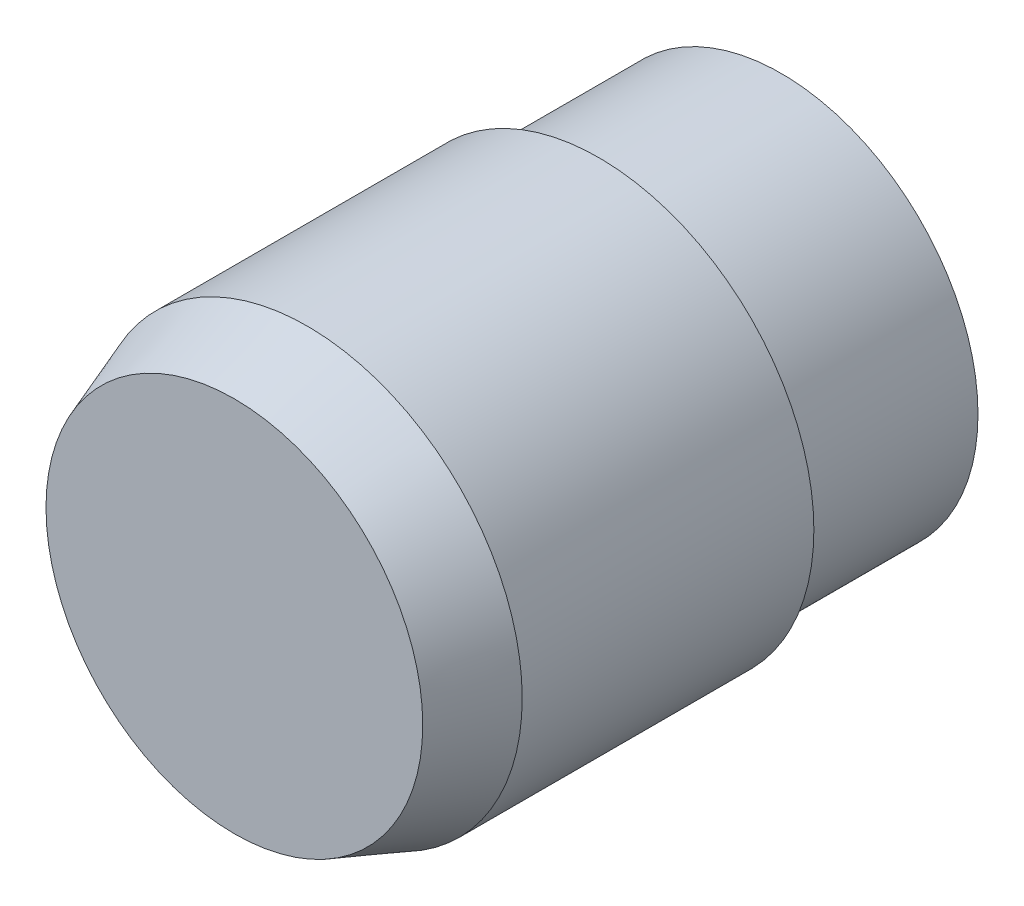
SolidWorks part; units mm, degrees
ref_plane "Front Plane" through (0, 0, 0) normal (0, 0, 1) x (1, 0, 0)
ref_plane "Top Plane" through (0, 0, 0) normal (0, 1, 0) x (1, 0, 0)
ref_plane "Right Plane" through (0, 0, 0) normal (1, 0, 0) x (0, 0, -1)
sketch "Sketch1" plane through (0, 0, 0) normal (0, 0, 1) x (1, 0, 0)
  circle A0 centre (0, 0) radius 10.7924
extrude "Boss-Extrude1" add sketch "Sketch1" along normal blind 10
sketch "Sketch2" plane through (0, 0, 10) normal (0, 0, 1) x (1, 0, 0)
  circle A0 centre (0, 0) radius 11.7894
extrude "Boss-Extrude2" add sketch "Sketch2" along normal blind 20
chamfer "Chamfer1" distance 4 angle 20 1 edges at (11.7894, 0, 30) first distance on face at (11.7894, 0, 30)
